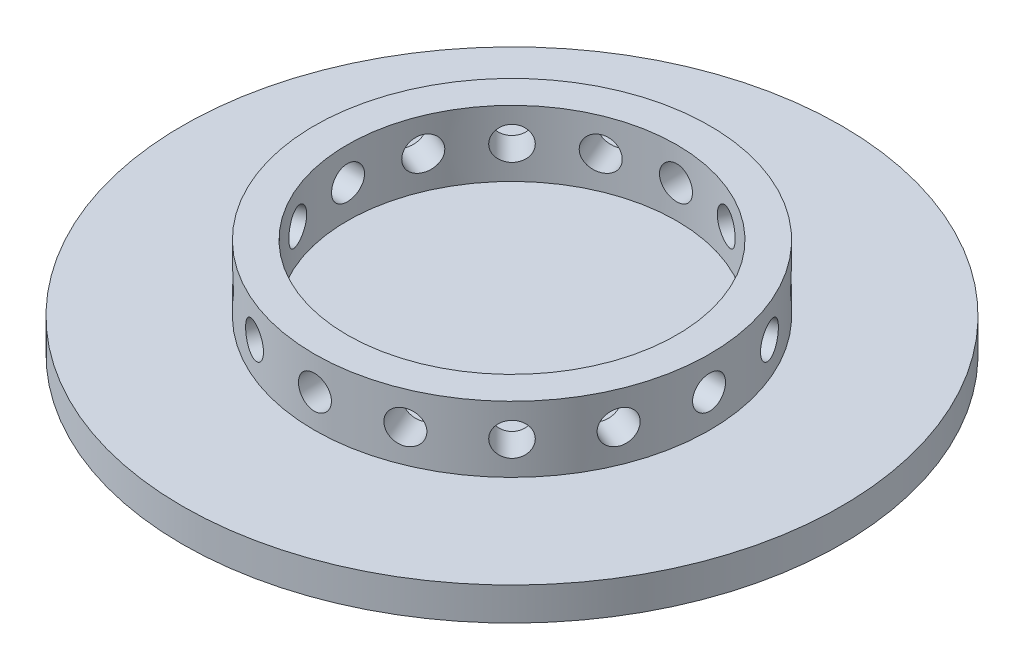
SolidWorks part; units mm, degrees
ref_plane "Front Plane" through (0, 0, 0) normal (0, 0, 1) x (1, 0, 0)
ref_plane "Top Plane" through (0, 0, 0) normal (0, 1, 0) x (1, 0, 0)
ref_plane "Right Plane" through (0, 0, 0) normal (1, 0, 0) x (0, 0, -1)
sketch "Sketch1" plane through (0, 0, 0) normal (0, 0, 1) x (1, 0, 0)
  line L0 (0, 0) -> (-58.3565, 0)
  line L1 (-63.5, 0) -> (-63.5, 6.35)
  line L2 (-63.5, 6.35) -> (-38.1, 6.35)
  line L3 (-38.1, 6.35) -> (-38.1, 19.05)
  line L4 (-38.1, 19.05) -> (-31.75, 19.05)
  line L5 (-31.75, 19.05) -> (-31.75, 6.35)
  line L6 (-31.75, 6.35) -> (0, 6.35)
  line L7 (0, 6.35) -> (0, 0)
  line L8 (-63.5, 0) -> (-61.9125, 0)
  line L9 (-61.9125, 0) -> (-61.9125, 2.54)
  line L10 (-61.9125, 2.54) -> (-58.3565, 2.54)
  line L11 (-58.3565, 2.54) -> (-58.3565, 0)
  dimension "D1" = 63.5
  dimension "D2" = 38.1
  dimension "D3" = 6.35
  dimension "D4" = 6.35
  dimension "D5" = 12.7
  dimension "D6" = 2.54
  dimension "D7" = 3.556
  dimension "D8" = 1.5875
revolve "Revolve1" add sketch "Sketch1" angle 360 about L7
ref_plane "Plane1" through (38.1, 0, 0) normal (1, 0, 0) x (0, 0, -1)
hole_wizard "1/4 (0.25) Diameter Hole1" positions "Sketch2" profile "Sketch3" hole size "1/4" standard "ANSI Inch"
sketch "Sketch2" plane through (38.1, 0, 0) normal (1, 0, 0) x (0, 0, -1)
  point P0 (0, 12.7)
  point P3 (0, 12.4224)
  point P4 (0, 0)
  point P6 (0, 0)
  dimension "D1" = 12.7
sketch "Sketch3" plane through (38.1, 12.7, 0) normal (0, 1, 0) x (0, 0, -1)
  line L0 (0, 0) -> (0, 40.0067)
  line L1 (0, 40.0067) -> (3.175, 38.099)
  line L2 (3.175, 38.099) -> (3.175, 0)
  line L5 (3.175, 0) -> (0, 0)
  line L10 (0, 40.0067) -> (-3.175, 38.099) construction
  line L11 (0, -6.35) -> (0, 107.95) construction
  dimension "Hole Dia." = 6.35
  dimension "Hole Depth" = 38.099
  dimension "Drill Angle" = 118
pattern_circular "CirPattern1" count 16 over 360 about axis through (0, 6.35, 0) along (0, 1, 0) of "1/4 (0.25) Diameter Hole1"
